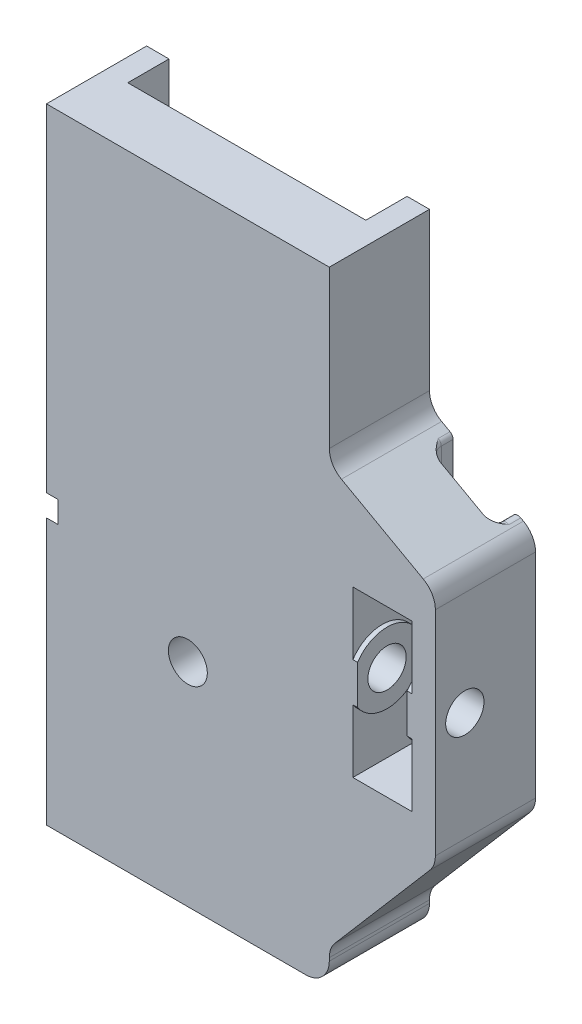
SolidWorks part; units mm, degrees
material "ABS"
ref_plane "前视基准面" through (0, 0, 0) normal (0, 0, 1) x (1, 0, 0)
ref_plane "上视基准面" through (0, 0, 0) normal (0, 1, 0) x (1, 0, 0)
ref_plane "右视基准面" through (0, 0, 0) normal (1, 0, 0) x (0, 0, -1)
other "Configuration Table"
sketch "草图1" plane through (0, 0, 0) normal (0, 0, 1) x (1, 0, 0)
  line L0 (0, 0) -> (0, 53)
  line L1 (0, 53) -> (24, 53)
  line L2 (24, 53) -> (24, 38.5)
  line L3 (24, 38.5) -> (33, 33.5)
  line L4 (33, 33.5) -> (33, 13.5)
  line L5 (33, 13.5) -> (24, 3)
  line L6 (24, 3) -> (24, 0)
  line L7 (24, 0) -> (0, 0)
  line L9 (26, 30.5) -> (31, 30.5)
  line L10 (26, 30.5) -> (26, 16.5)
  line L11 (26, 16.5) -> (31, 16.5)
  line L12 (31, 30.5) -> (31, 16.5)
  circle A0 centre (12, 18) radius 1.65
  dimension "D12" = 3.3
  dimension "D13" = 12
  dimension "D14" = 18
  dimension "D1" = 53
  dimension "D2" = 24
  dimension "D3" = 9
  dimension "D4" = 3
  dimension "D5" = 20
  dimension "D6" = 5
  dimension "D7" = 19.5
  dimension "D8" = 5
  dimension "D9" = 14
  dimension "D10" = 2
  dimension "D11" = 3
extrude "凸台-拉伸1" add sketch "草图1" along normal blind 8.5
sketch "草图2" plane through (0, 53, 0) normal (0, 1, 0) x (1, 0, 0)
  line L0 (24, 0) -> (0, 0) construction
  line L1 (1.9, 0) -> (22.1, 0)
  line L2 (1.9, 0) -> (1.9, -3.5)
  line L3 (1.9, -3.5) -> (22.1, -3.5)
  line L4 (22.1, 0) -> (22.1, -3.5)
  line L5 (0, -8.5) -> (0, 0) construction
  dimension "D1" = 3.5
  dimension "D2" = 1.9
  dimension "D3" = 20.2
extrude "切除-拉伸1" cut sketch "草图2" against normal offset from surface (50.1 mm away) 2.9 up to face at (12, 0, 4.25)
sketch "草图3" plane through (33, 0, 0) normal (1, 0, 0) x (0, 0, -1)
  line L0 (-8.5, 13.5) -> (-8.5, 33.5) construction
  circle A0 centre (-6, 23.5) radius 1.625
  dimension "D1" = 3.25
  dimension "D2" = 2.5
  dimension "D3" = 7
extrude "切除-拉伸2" cut sketch "草图3" against normal up to surface (7 mm away) up to face at (26, 23.5, 4.25)
sketch "草图4" plane through (26, 0, 0) normal (1, 0, 0) x (0, 0, -1)
  circle A0 centre (-6, 23.5) radius 1
  dimension "D1" = 2
extrude "切除-拉伸3" cut sketch "草图4" against normal up to surface (3.9 mm away) up to face at (22.1, 27.95, 1.75)
sketch "草图5" plane through (26, 0, 0) normal (1, 0, 0) x (0, 0, -1)
  line L0 (-8.5, 30.5) -> (-8.5, 16.5) construction
  line L1 (-8.5, 25.1583) -> (-8.5, 21.8417)
  circle A0 centre (-6, 23.5) radius 1 construction
  circle A1 centre (-6, 23.5) radius 1
  arc A2 (-8.5, 21.8417) -> (-8.5, 25.1583) centre (-6, 23.5) ccw
  dimension "D1" = 6
extrude "凸台-拉伸2" add sketch "草图5" along normal blind 0.4
sketch "草图6" plane through (31, 0, 0) normal (-1, 0, 0) x (0, 0, 1)
  line L1 (8.5, 21.8417) -> (8.5, 25.1583)
  line L2 (8.5, 21.8417) -> (8.5, 25.1583)
  circle A0 centre (6, 23.5) radius 1.625 construction
  arc A1 (8.5, 25.1583) -> (8.5, 21.8417) centre (6, 23.5) ccw
  arc A2 (8.5, 25.1583) -> (8.5, 21.8417) centre (6, 23.5) ccw
  circle A3 centre (6, 23.5) radius 1.625
  dimension "D1" = 0
extrude "凸台-拉伸3" add sketch "草图6" along normal blind 0.4
fillet "圆角1" radius 2 1 edges at (24, 3, 4.25)
fillet "圆角2" radius 2 4 edges at (24, 0, 4.25) (33, 13.5, 4.25) (33, 33.5, 4.25) (24, 38.5, 4.25)
sketch "草图7" plane through (33, 0, 0) normal (1, 0, 0) x (0, 0, -1)
  circle A0 centre (-6, 23.5) radius 1.625 construction
  circle A1 centre (-6, 23.5) radius 1.625
extrude "切除-拉伸4" cut sketch "草图7" against normal through all
sketch "草图8" plane through (0, 0, 0) normal (0, 0, -1) x (-1, 0, 0)
  line L1 (-31, 30.5) -> (-26, 30.5)
  line L2 (-31, 30.5) -> (-31, 39.3742)
  line L3 (-31, 39.3742) -> (-26, 39.3742)
  line L4 (-26, 30.5) -> (-26, 39.3742)
extrude "切除-拉伸5" cut sketch "草图8" against normal blind 2
fillet "圆角3" radius 0.5 2 edges at (31, 34.6111, 1) (26, 37.3889, 1)
fillet "圆角4" radius 1 4 edges at (25.9309, 37.3483, 2) (31.2464, 34.1923, 2) (26, 33.7973, 2) (31, 32.1307, 2)
sketch "Sketch1" plane through (0, 0, 0) normal (-1, 0, 0) x (0, 0, 1)
  line L1 (2.9689, 23.5) -> (4.4845, 20.875)
  line L2 (4.4845, 20.875) -> (7.5155, 20.875)
  line L3 (7.5155, 20.875) -> (9.0311, 23.5)
  line L4 (9.0311, 23.5) -> (7.5155, 26.125)
  line L5 (7.5155, 26.125) -> (4.4845, 26.125)
  line L6 (4.4845, 26.125) -> (2.9689, 23.5)
  circle A0 centre (6, 23.5) radius 2.625 construction
  dimension "D1" = 5.25
extrude "Cut-Extrude1" cut sketch "Sketch1" against normal blind 1
